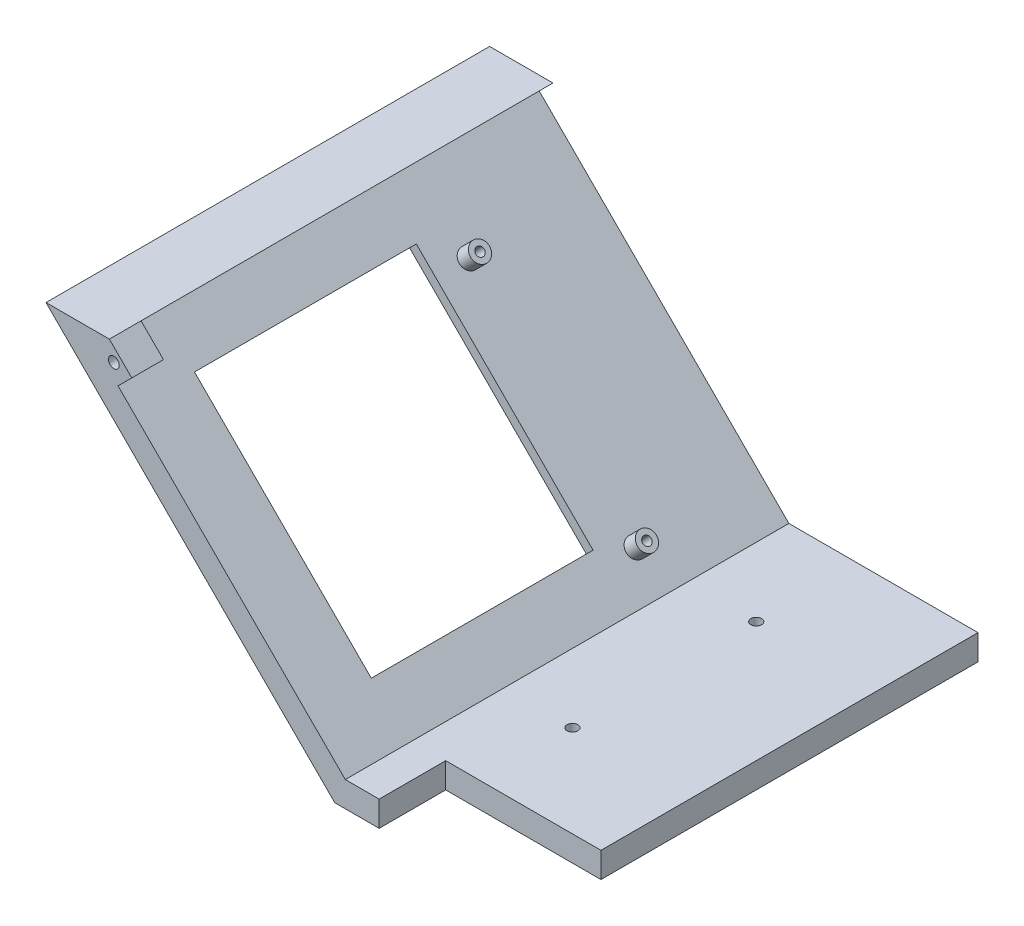
SolidWorks part; units mm, degrees
ref_plane "Plan de face" through (0, 0, 0) normal (0, 0, 1) x (1, 0, 0)
ref_plane "Plan de dessus" through (0, 0, 0) normal (0, 1, 0) x (1, 0, 0)
ref_plane "Plan de droite" through (0, 0, 0) normal (1, 0, 0) x (0, 0, -1)
sketch "Main-Sketch" plane through (0, 0, 0) normal (0, 0, 1) x (1, 0, 0)
  line L0 (0, 0) -> (0, 8)
  line L1 (0, 8) -> (-59.6863, 8)
  line L2 (-59.6863, 8) -> (-138.4931, 86.8069)
  line L3 (-154.15, 91.15) -> (-134.15, 91.15)
  line L4 (-154.15, 91.15) -> (-63, 0)
  line L5 (-63, 0) -> (0, 0)
  line L8 (-134.15, 91.15) -> (-138.4931, 86.8069)
  dimension "D1" = 8
  dimension "D2" = 8
  dimension "D3" = 63
  dimension "D4" = 135
  dimension "D5" = 20
  dimension "D6" = 154.15
extrude "Main-Extrusion" add sketch "Main-Sketch" along normal blind 140
sketch "Lcd-Sketch" plane through (0, 0, 0) normal (0, -1, 0) x (1, 0, 0)
  line L1 (0, 140) -> (-49, 140)
  line L2 (0, 140) -> (0, 119)
  line L3 (0, 119) -> (-49, 119)
  line L4 (-49, 140) -> (-49, 119)
  dimension "D1" = 21
  dimension "D2" = 49
extrude "Lcd-Hole" cut sketch "Lcd-Sketch" against normal through all
sketch "Upp-Fix-Sketch" plane through (0, 0, 140) normal (0, 0, 1) x (1, 0, 0)
  line L0 (-134.15, 91.15) -> (-138.4931, 86.8069)
  line L1 (-138.4931, 86.8069) -> (-131.4221, 79.7358)
  line L2 (-59.6863, 8) -> (-138.4931, 86.8069) construction
  line L3 (-131.4221, 79.7358) -> (-127.0789, 84.0789)
  line L4 (-127.0789, 84.0789) -> (-134.15, 91.15)
  dimension "D1" = 10
extrude "Up-Fix-Extrusion" add sketch "Upp-Fix-Sketch" against normal blind 10
hole_wizard "Fraisage pour vis à tête fraisée M31" positions "Esquisse7" profile "Esquisse6" countersink size "M3" standard "Ansi Metric" end condition up to next
sketch "Esquisse7" plane through (0, 0, 130) normal (0, 0, -1) x (-1, 0, 0)
  line L0 (127.0789, 84.0789) -> (134.15, 91.15) construction
  line L1 (131.4221, 79.7358) -> (127.0789, 84.0789) construction
  point P0 (132.7358, 85.4931)
  dimension "D1" = 3
  dimension "D2" = 5
sketch "Esquisse6" plane through (-132.7358, 85.4931, 130) normal (1, 0, 0) x (0, 1, 0)
  line L0 (0, 0) -> (0, 10)
  line L1 (0, 10) -> (1.7, 10)
  line L2 (1.7, 10) -> (1.7, 1.3)
  line L3 (1.7, 1.3) -> (3, 0)
  line L5 (3, 0) -> (0, 0)
  line L6 (-1.7, 1.3) -> (-3, 0) construction
  line L11 (0, -6.35) -> (0, 107.95) construction
  dimension "Diamètre du perçage jusqu'au prochain" = 3.4
  dimension "Profondeur du perçage jusqu'au prochain" = 10
  dimension "Diamètre du fraisage entrant" = 6
  dimension "Angle du fraisage entrant" = 90
sketch "MotorBoard-Hole-Sketch" plane through (-31.5, -31.5, 0) normal (-0.7071, -0.7071, 0) x (0, 0, 1)
  line L0 (0, 173.4533) -> (0, 44.5477) construction
  line L1 (120, 143.4533) -> (50, 143.4533)
  line L2 (120, 143.4533) -> (120, 64.5477)
  line L3 (120, 64.5477) -> (50, 64.5477)
  line L4 (50, 143.4533) -> (50, 64.5477)
  line L5 (140, 173.4533) -> (140, 44.5477) construction
  line L6 (140, 173.4533) -> (0, 173.4533) construction
  line L7 (140, 44.5477) -> (0, 44.5477) construction
  dimension "D1" = 50
  dimension "D2" = 20
  dimension "D3" = 30
  dimension "D4" = 20
extrude "MotorBoard-Hole" cut sketch "MotorBoard-Hole-Sketch" against normal through all
sketch "MotorBoard-Window-Sketch" plane through (-31.5, -31.5, 0) normal (-0.7071, -0.7071, 0) x (0, 0, 1)
  line L0 (120, 64.5477) -> (120, 143.4533) construction
  line L1 (128, 151.4533) -> (42, 151.4533)
  line L2 (128, 151.4533) -> (128, 56.5477)
  line L3 (128, 56.5477) -> (42, 56.5477)
  line L4 (42, 151.4533) -> (42, 56.5477)
  line L5 (120, 143.4533) -> (50, 143.4533) construction
  line L6 (50, 143.4533) -> (50, 64.5477) construction
  line L7 (50, 64.5477) -> (120, 64.5477) construction
  dimension "D1" = 8
  dimension "D2" = 8
  dimension "D3" = 8
  dimension "D4" = 8
extrude "MotorBoard-Window" cut sketch "MotorBoard-Window-Sketch" against normal blind 5
sketch "MotorBoard-Fix-Sketch" plane through (-25.8431, -25.8431, 0) normal (0.7071, 0.7071, 0) x (0, 0, -1)
  line L0 (-140, 47.8614) -> (-140, 149.3112) construction
  line L1 (-140, 47.8614) -> (0, 47.8614) construction
  circle A0 centre (-39.5, 60.3614) radius 3
  circle A1 centre (-39.5, 134.8614) radius 3
  dimension "D1" = 6
  dimension "D2" = 74.5
  dimension "D3" = 100.5
  dimension "D4" = 12.5
extrude "MotorBoard-Fix-Extrusion" add sketch "MotorBoard-Fix-Sketch" along normal blind 5
sketch "MotorBoard-Fix-Hole-Sketch" plane through (-22.3076, -22.3076, 0) normal (0.7071, 0.7071, 0) x (0, 0, -1)
  circle A0 centre (-39.5, 60.3614) radius 1.35
  circle A1 centre (-39.5, 134.8614) radius 1.35
  circle A2 centre (-39.5, 134.8614) radius 3 construction
  dimension "D1" = 2.7
extrude "MotorBoard-Fix-Hole" cut sketch "MotorBoard-Fix-Hole-Sketch" against normal through all
hole_wizard "Fraisage pour vis à tête fraisée M32" positions "Esquisse8" profile "Esquisse9" countersink size "M3" standard "Ansi Metric" end condition through all
sketch "Esquisse8" plane through (0, 0, 0) normal (0, -1, 0) x (-1, 0, 0)
  line L0 (63, -140) -> (63, 0) construction
  line L2 (63, -140) -> (49, -140) construction
  point P0 (38, -90)
  point P2 (38, -32)
  point P5 (0, 0)
  point P6 (0, 0)
  dimension "D1" = 58
  dimension "D2" = 25
  dimension "D3" = 50
sketch "Esquisse9" plane through (-38, 0, 90) normal (1, 0, 0) x (0, 0, -1)
  line L0 (0, 0) -> (0, 91.15)
  line L1 (0, 91.15) -> (1.7, 91.15)
  line L2 (1.7, 91.15) -> (1.7, 1.45)
  line L3 (1.7, 1.45) -> (3.15, 0)
  line L5 (3.15, 0) -> (0, 0)
  line L6 (-1.7, 1.45) -> (-3.15, 0) construction
  line L11 (0, -6.35) -> (0, 107.95) construction
  dimension "Diamètre du perçage jusqu'au prochain" = 3.4
  dimension "Profondeur du perçage jusqu'au prochain" = 91.15
  dimension "Diamètre du fraisage entrant" = 6.3
  dimension "Angle du fraisage entrant" = 90
